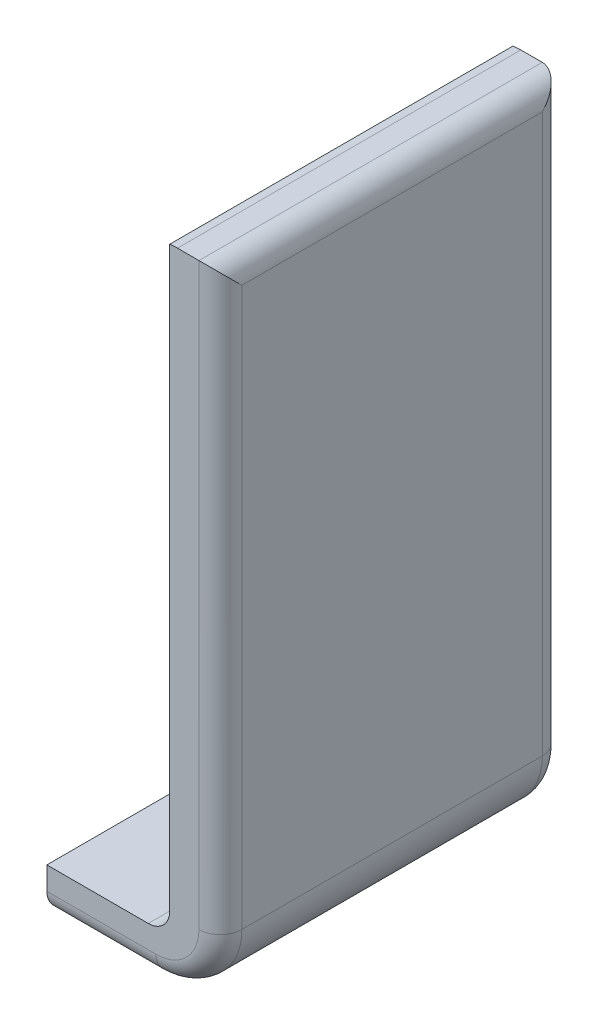
SolidWorks part; units mm, degrees
ref_plane "Front Plane" through (0, 0, 0) normal (0, 0, 1) x (1, 0, 0)
ref_plane "Top Plane" through (0, 0, 0) normal (0, 1, 0) x (1, 0, 0)
ref_plane "Right Plane" through (0, 0, 0) normal (1, 0, 0) x (0, 0, -1)
sketch "Sketch1" plane through (0, 0, 0) normal (0, 0, 1) x (1, 0, 0)
  line L0 (0, 0) -> (21.5609, 0)
  line L1 (21.5609, 0) -> (21.5609, 30)
  line L2 (21.5609, 30) -> (16.5609, 30)
  line L3 (16.5609, 30) -> (16.5609, 5)
  line L4 (16.5609, 5) -> (0, 5)
  line L5 (0, 5) -> (0, 0)
  dimension "D1" = 30
  dimension "D2" = 5
  dimension "D3" = 5
extrude "Boss-Extrude1" add sketch "Sketch1" along normal blind 16
fillet "Fillet1" radius 1 6 edges at (10.7805, 0, 0) (0, 0, 8) (10.7805, 0, 16) (21.5609, 15, 0) (21.5609, 15, 16) (21.5609, 30, 8)
fillet "Fillet2" radius 3 3 edges at (21.268, 0.2929, 0.2929) (21.268, 0.2929, 15.7071) (21.5609, 0, 8)
fillet "Fillet3" radius 3 1 edges at (16.5609, 5, 8)
fillet "Fillet4" radius 3 2 edges at (16.5609, 30, 8) (0, 5, 8)
sketch "Sketch2" plane through (0, 0, 0) normal (0, -1, 0) x (1, 0, 0)
  line L0 (1, 15) -> (0, 16) construction
  line L1 (0, 16) -> (7.4258, 16)
  line L2 (0, 16) -> (0, 0)
  line L3 (0, 0) -> (7.4258, 0)
  line L4 (7.4258, 16) -> (7.4258, 0)
  line L5 (18.5609, 0) -> (0, 0) construction
extrude "Cut-Extrude1" cut sketch "Sketch2" against normal blind 13
fillet "Fillet5" radius 3 1 edges at (7.4258, 5, 8)
sketch "Sketch3" plane through (0, 0, 0) normal (0, 0, -1) x (-1, 0, 0)
  line L1 (-19.1987, 30.846) -> (-1.5234, 30.846)
  line L2 (-19.1987, 30.846) -> (-19.1987, 2.0631)
  line L3 (-19.1987, 2.0631) -> (-1.5234, 2.0631)
  line L4 (-1.5234, 30.846) -> (-1.5234, 2.0631)
extrude "Cut-Extrude2" cut sketch "Sketch3" against normal blind 33
fillet "Fillet6" radius 1 1 edges at (19.1987, 2.0631, 8)
sketch "Sketch4" plane through (0, 2.0631, 0) normal (0, 1, 0) x (1, 0, 0)
  line L1 (6.6772, 0.8308) -> (13.4717, 0.8308)
  line L2 (6.6772, 0.8308) -> (6.6772, -17.2459)
  line L3 (6.6772, -17.2459) -> (13.4717, -17.2459)
  line L4 (13.4717, 0.8308) -> (13.4717, -17.2459)
extrude "Cut-Extrude3" cut sketch "Sketch4" against normal blind 33
